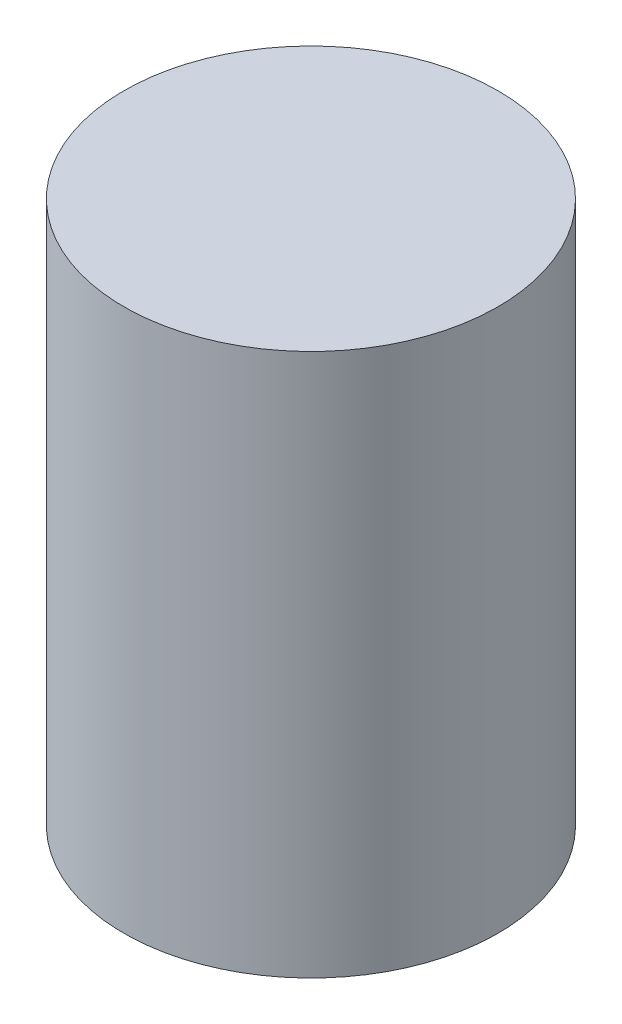
SolidWorks part; units mm, degrees
ref_plane "Front Plane" through (0, 0, 0) normal (0, 0, 1) x (1, 0, 0)
ref_plane "Top Plane" through (0, 0, 0) normal (0, 1, 0) x (1, 0, 0)
ref_plane "Right Plane" through (0, 0, 0) normal (1, 0, 0) x (0, 0, -1)
sketch "Sketch1" plane through (0, 0, 0) normal (0, 1, 0) x (1, 0, 0)
  circle A0 centre (0, 0) radius 31.0288
  circle A1 centre (0, 0) radius 26.0288
  dimension "D2" = 52.0576
  dimension "D1" = 5
extrude "Boss-Extrude1" add sketch "Sketch1" along normal blind 90 contours A0
extrude "Cut-Extrude2" cut sketch "Sketch1<5>" along normal blind 85 contours A1
sketch "Sketch1<5>" plane through (0, 0, 0) normal (0, 1, 0) x (1, 0, 0) same geometry as "Sketch1"
equation "\"insidebladediameter\"=0.0361727"
equation "\"height\"=0.02"
equation "\"bladethickness\"= 0.001"
equation "\"insidebladeradius\"= \"insidebladediameter\" / 2"
equation "\"bladewidth\"= 0.01"
equation "\"bladelength\"=0.06"
equation "\"bladetipradius\"=0.0075"
equation "\"fusedistance\"= \"insidebladeradius\" - 0.001"
equation "\"numberofblades\"= 6"
equation "\"roddiameter\"=0.0226166"
equation "\"roddepth\"= 0.01"
equation "\"wellthickness\"= 0.005"
equation "\"D1@Sketch1\"=\"wellthickness\""
equation "\"D1@Boss-Extrude1\"=\"wellheight\""
equation "\"wellheight\"= 0.09"
equation "\"welldiameter\"= ( \"insidebladediameter\" + 2 * \"bladelength\" ) * 1 / 3"
equation "\"D2@Sketch1\"=\"welldiameter\""
equation "\"insidewellheight\"= \"wellheight\" - \"wellthickness\""
equation "\"D1@Cut-Extrude2\"=\"insidewellheight\""
